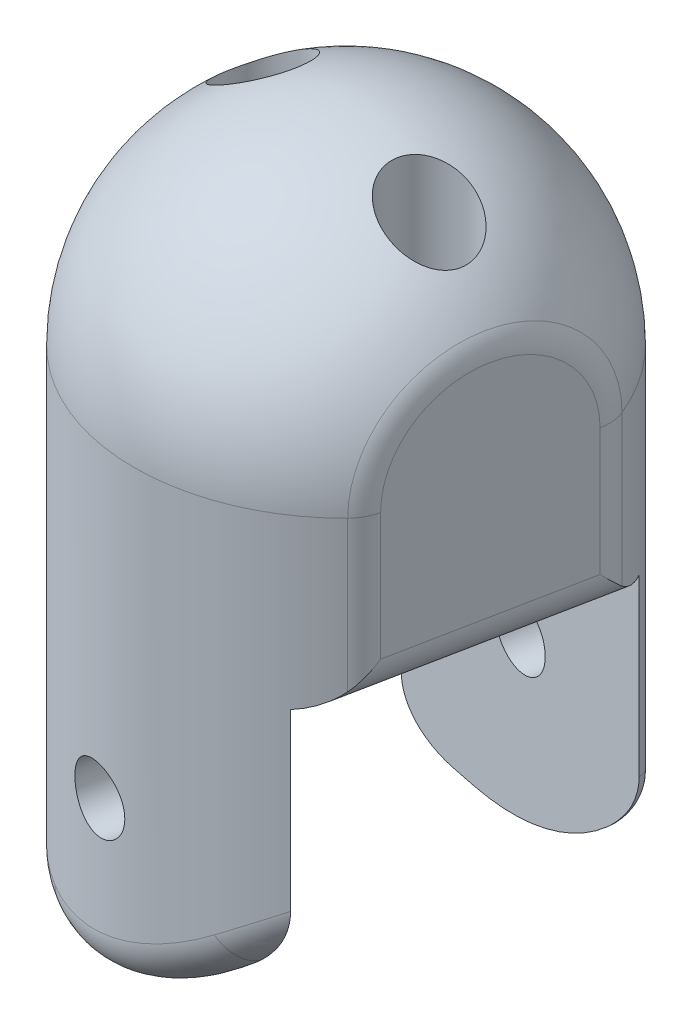
SolidWorks part; units mm, degrees
ref_plane "Front Plane" through (0, 0, 0) normal (0, 0, 1) x (1, 0, 0)
ref_plane "Top Plane" through (0, 0, 0) normal (0, 1, 0) x (1, 0, 0)
ref_plane "Right Plane" through (0, 0, 0) normal (1, 0, 0) x (0, 0, -1)
sketch "Sketch1" plane through (0, 0, 0) normal (0, 1, 0) x (1, 0, 0)
  circle A0 centre (0, 0) radius 12.7
  dimension "D1" = 25.4
extrude "Body" add sketch "Sketch1" along normal blind 22.86
fillet "Fillet1" radius 12.7 1 edges at (0, 22.86, 12.7) conic radius 12.7
sketch "Sketch2" plane through (0, 0, 0) normal (0, -1, 0) x (1, 0, 0)
  line L0 (6.228, 1.239) -> (0, 0) construction
  line L1 (0, 0) -> (-12.4559, -2.4779) construction
  line L2 (6.228, 1.239) -> (12.4559, 2.4779) construction
  line L3 (0, 0) -> (-2.4779, 12.4559) construction
  circle A0 centre (-6.228, -1.239) radius 2.413
  circle A1 centre (0, 0) radius 12.7 construction
  circle A4 centre (6.228, 1.239) radius 2.413
  dimension "D1" = 6.35
  dimension "D5" = 6.35
extrude "StringFeed" cut sketch "Sketch2" against normal blind 50.8
sketch "Sketch6" plane through (0, 0, 0) normal (0, -1, 0) x (1, 0, 0)
  line L2 (-7.1608, -10.4887) -> (10.6298, -6.9496)
  line L3 (0, 0) -> (-12.4559, -2.4779) construction
  circle A0 centre (0, 0) radius 12.7 construction
  arc A1 (-7.1608, -10.4887) -> (10.6298, -6.9496) centre (0, 0) ccw
  point P4 (1.7345, -8.7191)
  dimension "D1" = 8.89
extrude "Boss-Extrude2" add sketch "Sketch6" along normal blind 18.288
ref_plane "Plane8" through (0, 0, 0) normal (-0.1951, 0, 0.9808) x (-0.9808, 0, -0.1951)
mirror "SideMirror" about plane through (0, 0, 0) normal (-0.1951, 0, 0.9808) of "Boss-Extrude2"
sketch "Sketch9" plane through (1.7345, 0, -8.7191) normal (-0.1951, 0, 0.9808) x (0.9808, 0, 0.1951)
  line L0 (0, 0) -> (0, -8.382) construction
  line L2 (-9.0696, -18.288) -> (-9.0696, 0) construction
  line L3 (-9.0696, -9.144) -> (9.0696, -9.144) construction
  line L4 (9.0696, -18.288) -> (9.0696, 0) construction
  circle A0 centre (0, -8.382) radius 1.905
extrude "Cut-Extrude3" cut sketch "Sketch9" against normal blind 70.866 contours A0
mirror "HoleMirror" about plane through (0, 0, 0) normal (-0.1951, 0, 0.9808) of "Cut-Extrude3"
ref_plane "Plane11" through (0, 0, 0) normal (0.9808, 0, 0.1951) x (-0.1951, 0, 0.9808)
sketch "Sketch12" plane through (0, 0, 0) normal (0, -1, 0) x (1, 0, 0)
  line L0 (-12.0396, 4.042) -> (-9.576, -8.3421)
  line L1 (0, 0) -> (-12.4559, -2.4779) construction
  line L2 (5.5355, -27.8257) -> (-5.5355, 27.8257) construction
  arc A0 (-10.6298, 6.9496) -> (-7.1608, -10.4887) centre (0, 0) ccw construction
  arc A1 (-12.0396, 4.042) -> (-9.576, -8.3421) centre (0, 0) ccw
  point P9 (-10.8078, -2.15)
  dimension "D1" = 11.0196
extrude "Cut-Extrude6" cut sketch "Sketch12" against normal through all
sketch "Sketch14" plane through (1.7345, 0, -8.7191) normal (-0.1951, 0, 0.9808) x (0.9808, 0, 0.1951)
  line L0 (2.4523, -18.288) -> (9.0696, -12.1996)
  line L1 (9.0696, -18.288) -> (-9.0696, -18.288) construction
  line L2 (9.0696, -18.288) -> (9.0696, 0) construction
  line L3 (9.0696, -12.1996) -> (9.0696, -18.288)
  line L4 (9.0696, -18.288) -> (2.4523, -18.288)
  dimension "D1" = 6.0884
  dimension "D2" = 6.6173
extrude "Cut-Extrude8" cut sketch "Sketch14" against normal through all both and the other way through all
mirror "Mirror1" about plane through (0, 0, 0) normal (0.9808, 0, 0.1951) of "Cut-Extrude6"
fillet "Fillet31" radius 15.24 1 edges at (0.3223, -18.288, 10.9488)
fillet "Fillet9" radius 2.54 3 edges at (10.8078, 16.4734, 2.15) (9.576, 5.08, 8.3421) (10.8078, 0, 2.15)
fillet "Fillet32" radius 2.54 3 edges at (-8.5008, -18.288, 9.4353) (5.9218, -13.1837, 11.2349) (-2.5754, -17.9056, 12.4361)
fillet "Fillet8" radius 2.54 3 edges at (-12.0396, 5.08, 4.042) (-10.8078, 0, -2.15) (-10.8078, 16.4734, -2.15)
fillet "Fillet12" radius 15.24 1 edges at (4.4881, -18.288, -9.9918)
fillet "Fillet34" radius 2.54 3 edges at (-4.2425, -18.288, -11.9704) (5.8252, -16.5836, -11.2853) (9.7708, -13.1837, -8.113)
